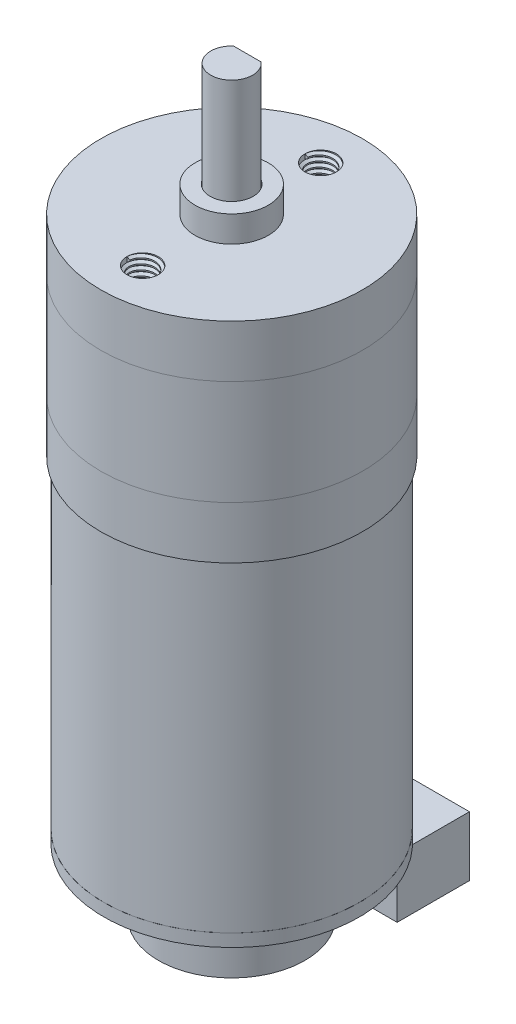
SolidWorks part; units mm, degrees
ref_plane "Front Plane" through (0, 0, 0) normal (0, 0, 1) x (1, 0, 0)
ref_plane "Top Plane" through (0, 0, 0) normal (0, 1, 0) x (1, 0, 0)
ref_plane "Right Plane" through (0, 0, 0) normal (1, 0, 0) x (0, 0, -1)
sketch "Sketch1" plane through (0, 0, 0) normal (0, 1, 0) x (1, 0, 0)
  circle A0 centre (0, 0) radius 12.5
  dimension "D1" = 25
extrude "Boss-Extrude1" add sketch "Sketch1" against normal blind 5
extrude "Boss-Extrude2" add sketch "Sketch1<2>" against normal blind 10 from offset 5 separate body offset against normal yes
sketch "Sketch1<2>" plane through (0, 0, 0) normal (0, 1, 0) x (1, 0, 0) same geometry as "Sketch1"
extrude "Boss-Extrude3" add sketch "Sketch1<3>" against normal blind 5 from offset 15 separate body offset against normal yes
sketch "Sketch1<3>" plane through (0, 0, 0) normal (0, 1, 0) x (1, 0, 0) same geometry as "Sketch1"
sketch "Sketch5" plane through (0, 0, 0) normal (0, 1, 0) x (1, 0, 0)
  line L0 (0, -12.5) -> (0, 12.5) construction
  circle A0 centre (0, 0) radius 12.5 construction
  circle A1 centre (0, 8.5) radius 1.5
  circle A2 centre (0, -8.5) radius 1.5
  dimension "D1" = 3
  dimension "D2" = 8.5
  dimension "D3" = 8.5
  dimension "D4" = 3
extrude "Cut-Extrude2" cut sketch "Sketch5" against normal blind 4.5
thread "Thread1" pitch 0.5 method extrude profile "Thread Profile1" start angle 0, offset 0, length 0, pitch 0.5, diameter 3
ref_plane "Plane1" through (-1.5, 0, -8.5) normal (0, 0, 1) x (-1, 0, 0)
sketch "Thread Profile1" plane through (-1.5, 0, -8.5) normal (0, 0, 1) x (-1, 0, 0)
  line L0 (0, 0) -> (0, 0.5) construction
  line L11 (0, 0) -> (0, 0.4375)
  line L12 (0, 0.4375) -> (-0.2706, 0.2812)
  line L13 (-0.2706, 0.2812) -> (-0.2706, 0.1562)
  line L15 (-0.2706, 0.1562) -> (0, 0)
  line L17 (-0.2706, 0.2187) -> (0, 0.2187) construction
  point P2 (0, 0)
  dimension "Pitch" = 0.5
  dimension "Profile_Angle" = 60
  dimension "Profile_Land" = 0.125
  dimension "Profile_Height" = 0.2706
thread "Thread2" pitch 0.5 method extrude profile "Thread Profile2" start angle 0, offset 0, length 0, pitch 0.5, diameter 3
ref_plane "Plane2" through (-1.5, 0, 8.5) normal (0, 0, 1) x (-1, 0, 0)
sketch "Thread Profile2" plane through (-1.5, 0, 8.5) normal (0, 0, 1) x (-1, 0, 0)
  line L0 (0, 0) -> (0, 0.5) construction
  line L11 (0, 0) -> (0, 0.4375)
  line L12 (0, 0.4375) -> (-0.2706, 0.2812)
  line L13 (-0.2706, 0.2812) -> (-0.2706, 0.1562)
  line L15 (-0.2706, 0.1562) -> (0, 0)
  line L17 (-0.2706, 0.2187) -> (0, 0.2187) construction
  point P2 (0, 0)
  dimension "Pitch" = 0.5
  dimension "Profile_Angle" = 60
  dimension "Profile_Land" = 0.125
  dimension "Profile_Height" = 0.2706
sketch "Sketch2" plane through (0, 0, 0) normal (0, 1, 0) x (1, 0, 0)
  circle A0 centre (0, 0) radius 2
  dimension "D1" = 4
extrude "Boss-Extrude4" add sketch "Sketch2" along normal blind 12.5 and the other way blind 60 separate body
sketch "Sketch3" plane through (0, 12.5, 0) normal (0, 1, 0) x (1, 0, 0)
  line L0 (0, 0) -> (0, 2) construction
  line L6 (-2, 1.5) -> (2, 1.5)
  line L7 (-2, 1.5) -> (-2, 2.5)
  line L8 (-2, 2.5) -> (2, 2.5)
  line L9 (2, 1.5) -> (2, 2.5)
  line L10 (-2, 1.5) -> (2, 2.5) construction
  line L11 (-2, 2.5) -> (2, 1.5) construction
  circle A1 centre (0, 0) radius 2 construction
  dimension "D1" = 1
  dimension "D2" = 4
extrude "Cut-Extrude1" cut sketch "Sketch3" against normal blind 7.5
sketch "Sketch4" plane through (0, 0, 0) normal (0, 1, 0) x (1, 0, 0)
  circle A0 centre (0, 0) radius 2.05
  circle A1 centre (0, 0) radius 3.5
  dimension "D1" = 4.1
  dimension "D2" = 7
extrude "Boss-Extrude5" add sketch "Sketch4" along normal blind 2.5 separate body
sketch "Sketch11" plane through (0, -20, 0) normal (0, -1, 0) x (1, 0, 0)
  circle A0 centre (0, 0) radius 12.2
  dimension "D1" = 24.4
extrude "Motor" add sketch "Sketch11" along normal blind 30.8 separate body
sketch "Sketch12" plane through (0, -50.8, 0) normal (0, -1, 0) x (1, 0, 0)
  circle A0 centre (0, 0) radius 12.21
  dimension "D1" = 24.42
extrude "Boss-Extrude7" add sketch "Sketch12" along normal blind 1.2 separate body
sketch "Sketch13" plane through (0, -52, 0) normal (0, -1, 0) x (1, 0, 0)
  line L0 (0, 0) -> (0, -12.21) construction
  line L2 (-8.75, -13.95) -> (8.75, -13.95)
  line L3 (-8.75, -13.95) -> (-8.75, -7.05)
  line L4 (-8.75, -7.05) -> (8.75, -7.05)
  line L5 (8.75, -13.95) -> (8.75, -7.05)
  line L6 (-8.75, -13.95) -> (8.75, -7.05) construction
  line L7 (-8.75, -7.05) -> (8.75, -13.95) construction
  circle A0 centre (0, 0) radius 12.21 construction
  point P5 (0, -10.5)
  dimension "D1" = 17.5
  dimension "D2" = 6.9
  dimension "D3" = 10.5
extrude "Boss-Extrude8" add sketch "Sketch13" along normal blind 5.7 separate body
sketch "Sketch14" plane through (0, -52, 0) normal (0, -1, 0) x (1, 0, 0)
  circle A0 centre (0, 0) radius 7
  circle A1 centre (0, 0) radius 2.05
  dimension "D1" = 14
  dimension "D2" = 4.1
extrude "Boss-Extrude9" add sketch "Sketch14" along normal blind 6 from offset 0.2 separate body
sketch "Sketch15" plane through (0, 0, -13.95) normal (0, 0, -1) x (-1, 0, 0)
  line L0 (0, -57.7) -> (0, -52) construction
  line L1 (8.75, -57.7) -> (-8.75, -57.7) construction
  line L2 (-12.21, -52) -> (12.21, -52) construction
  line L3 (8.75, -57.7) -> (8.75, -52) construction
  line L4 (8.25, -52.6022) -> (-8.25, -52.6022)
  line L5 (8.25, -52.6022) -> (8.25, -57.0978)
  line L6 (8.25, -57.0978) -> (-8.25, -57.0978)
  line L7 (-8.25, -52.6022) -> (-8.25, -57.0978)
  line L8 (8.25, -52.6022) -> (-8.25, -57.0978) construction
  line L9 (8.25, -57.0978) -> (-8.25, -52.6022) construction
  line L10 (-7.25, -57.0978) -> (-5.75, -57.0978)
  line L11 (7.25, -57.7) -> (5.75, -57.7)
  line L12 (7.25, -57.7) -> (7.25, -57.0978)
  line L13 (7.25, -57.0978) -> (5.75, -57.0978)
  line L14 (5.75, -57.7) -> (5.75, -57.0978)
  line L19 (-5.75, -57.7) -> (-5.75, -57.0978)
  line L20 (-7.25, -57.7) -> (-5.75, -57.7)
  line L21 (-7.25, -57.7) -> (-7.25, -57.0978)
  point P6 (0, -54.85)
  line M16 (-8.75, -57.7) -> (8.75, -57.7)
  dimension "D1" = 0.5
  dimension "D2" = 0.6022
  dimension "D3" = 1.5
  dimension "D4" = 1.5
extrude "Cut-Extrude3" cut sketch "Sketch15" against normal blind 5 contours L4 L7 L6 L5 | L14 L12 L6 M16 | L21 L19 L6 M16 region at (0, -54.85, -13.95) region at (-6.5, -57.3989, -13.95) region at (6.5, -57.3989, -13.95)
sketch "Sketch16" plane through (0, 0, -8.95) normal (0, 0, -1) x (-1, 0, 0)
  line L0 (0, -57.0978) -> (0, -52.6022) construction
  line L1 (5.75, -57.0978) -> (-5.75, -57.0978) construction
  line L2 (8.25, -52.6022) -> (-8.25, -52.6022) construction
  line L3 (4.06, -54.7878) -> (4.06, -55.4078)
  line L8 (5.75, -57.0978) -> (-5.75, -57.0978) construction
  line L9 (1.56, -54.7878) -> (0.94, -54.7878)
  line L10 (4.06, -54.7878) -> (3.44, -54.7878)
  line L11 (1.56, -54.7878) -> (1.56, -55.4078)
  line L12 (1.56, -55.4078) -> (0.94, -55.4078)
  line L13 (0.94, -54.7878) -> (0.94, -55.4078)
  line L14 (1.56, -54.7878) -> (0.94, -55.4078) construction
  line L15 (1.56, -55.4078) -> (0.94, -54.7878) construction
  line L16 (3.44, -54.7878) -> (3.44, -55.4078)
  line L17 (4.06, -55.4078) -> (3.44, -55.4078)
  line L18 (6.56, -54.7878) -> (6.56, -55.4078)
  line L19 (6.56, -54.7878) -> (5.94, -54.7878)
  line L20 (5.94, -54.7878) -> (5.94, -55.4078)
  line L21 (6.56, -55.4078) -> (5.94, -55.4078)
  line L22 (-0.94, -54.7878) -> (-0.94, -55.4078)
  line L23 (-0.94, -54.7878) -> (-1.56, -54.7878)
  line L24 (-1.56, -54.7878) -> (-1.56, -55.4078)
  line L25 (-0.94, -55.4078) -> (-1.56, -55.4078)
  line L26 (-3.44, -54.7878) -> (-3.44, -55.4078)
  line L27 (-3.44, -54.7878) -> (-4.06, -54.7878)
  line L28 (-4.06, -54.7878) -> (-4.06, -55.4078)
  line L29 (-3.44, -55.4078) -> (-4.06, -55.4078)
  line L30 (-5.94, -54.7878) -> (-5.94, -55.4078)
  line L31 (-5.94, -54.7878) -> (-6.56, -54.7878)
  line L32 (-6.56, -54.7878) -> (-6.56, -55.4078)
  line L33 (-5.94, -55.4078) -> (-6.56, -55.4078)
  point P6 (1.25, -55.0978)
  dimension "D1" = 2
  dimension "D2" = 1.25
  dimension "D3" = 0.62
  dimension "D4" = 0.62
  dimension "D7" = 0.94
  dimension "D8" = 1.88
  dimension "D5" = 3
  dimension "D6" = 4
extrude "Boss-Extrude10" add sketch "Sketch16" along normal blind 4 separate body
